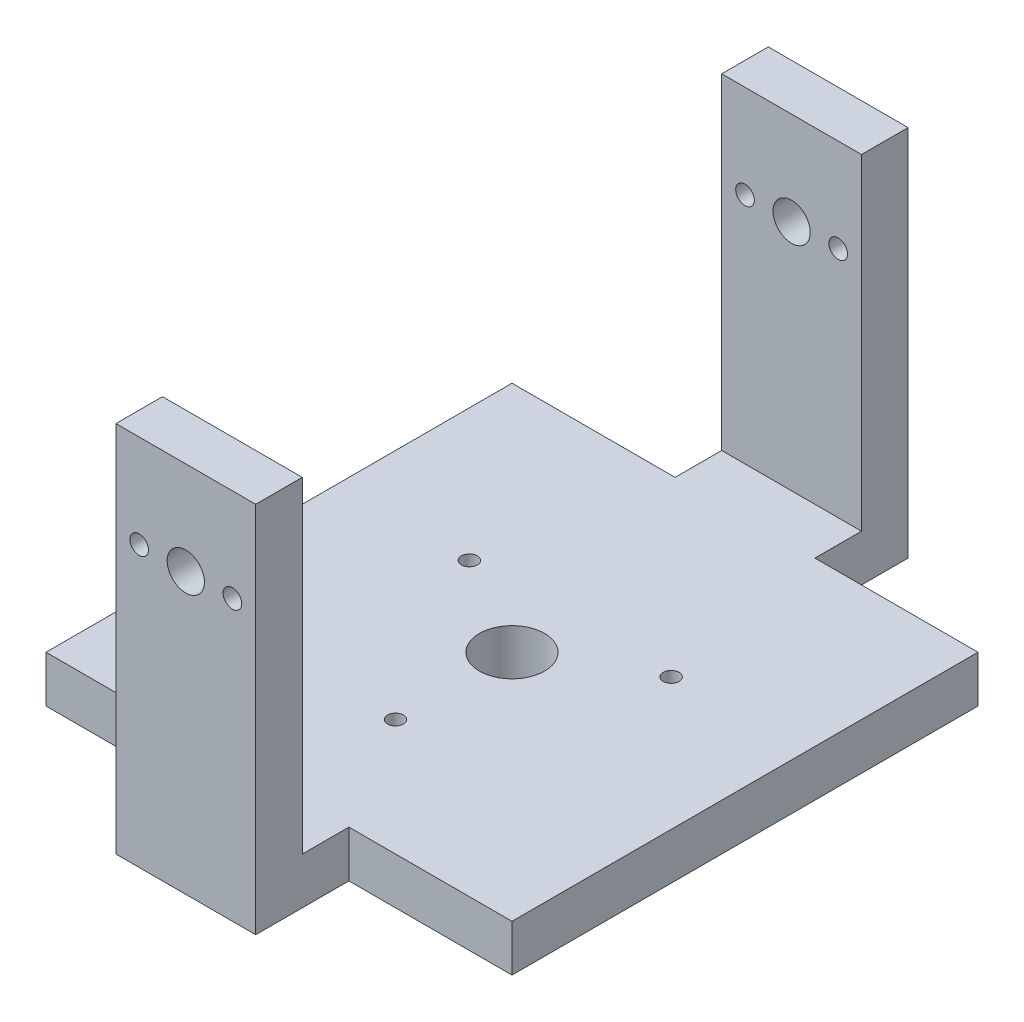
SolidWorks part; units mm, degrees
ref_plane "Plano frontal" through (0, 0, 0) normal (0, 0, 1) x (1, 0, 0)
ref_plane "Plano superior" through (0, 0, 0) normal (0, 1, 0) x (1, 0, 0)
ref_plane "Plano direito" through (0, 0, 0) normal (1, 0, 0) x (0, 0, -1)
sketch "Esboço1" plane through (0, 0, 0) normal (0, 0, 1) x (1, 0, 0)
  line L17 (-15, -50) -> (15, -50)
  line L18 (-15, -50) -> (-15, 20)
  line L19 (-15, 20) -> (15, 20)
  line L20 (15, -50) -> (15, 20)
  line L27 (-15, -50) -> (15, -50)
  line L28 (-15, -50) -> (-15, -60)
  line L29 (-15, -60) -> (15, -60)
  line L30 (15, -50) -> (15, -60)
  line L32 (-50, -50) -> (50, -50)
  line L33 (-50, -50) -> (-50, -60)
  line L34 (-50, -60) -> (50, -60)
  line L35 (50, -50) -> (50, -60)
  circle A0 centre (10, 0) radius 2
  circle A1 centre (-10, 0) radius 2
  circle A2 centre (0, 0) radius 4
extrude "Ressalto-extrusão1" add sketch "Esboço1" along normal blind 10 contours L17 L20 L19 L18 region at (0, -15.5586, 0)
extrude "Ressalto-extrusão3" add sketch "Esboço1<4>" along normal blind 70 contours L30 L17 L28 L29 region at (0, -55, 0)
sketch "Esboço1<4>" plane through (0, 0, 0) normal (0, 0, 1) x (1, 0, 0) same geometry as "Esboço1"
ref_plane "Plano1" through (0, 0, 70) normal (0, 0, 1) x (1, 0, 0)
extrude "Ressalto-extrusão5" add sketch "Esboço1<6>" against normal blind 50 from surface contours L33 L34 L28 L32 | L35 L32 L30 L34 region at (-32.5, -55, 0) region at (32.5, -55, 0) starting at plane "Plano1"
sketch "Esboço1<6>" plane through (0, 0, 0) normal (0, 0, 1) x (1, 0, 0) same geometry as "Esboço1"
mirror "Espelhar2" about plane through (0, 0, 70) normal (0, 0, 1) of "Ressalto-extrusão5", "Ressalto-extrusão3", "Ressalto-extrusão1"
sketch "Esboço3" plane through (0, -50, 0) normal (0, 1, 0) x (1, 0, 0)
  circle A0 centre (0, -70) radius 7
  circle A1 centre (0, -95) radius 3.3
  circle A2 centre (-21.6506, -57.5) radius 3.3
  circle A3 centre (21.6506, -57.5) radius 3.3
  point P11 (0, -70)
  dimension "D1" = 3
extrude "Corte-extrusão1" cut sketch "Esboço3" against normal blind 10 contours A0
sketch "Esboço7" plane through (0, -60, 0) normal (0, -1, 0) x (-1, 0, 0)
  circle A0 centre (0, -95) radius 3.3
  circle A1 centre (-21.6506, -57.5) radius 3.3
  circle A2 centre (21.6506, -57.5) radius 3.3
hole_wizard "Rebaixo para parafuso Allen sextavado de M34" positions "Esboço10" profile "Esboço11" counterbore size "M3" standard "ISO" end condition up to next
sketch "Esboço10" plane through (0, -60, 0) normal (0, -1, 0) x (-1, 0, 0)
  point P0 (-21.6506, -57.5)
  point P3 (21.6506, -57.5)
  point P6 (0, -95)
sketch "Esboço11" plane through (21.6506, -60, 57.5) normal (1, 0, 0) x (0, 0, -1)
  line L0 (0, 0) -> (0, 10)
  line L1 (0, 10) -> (1.7, 10)
  line L3 (1.7, 10) -> (1.7, 3.4)
  line L4 (3.25, 3.4) -> (1.7, 3.4)
  line L5 (3.25, 3.4) -> (3.25, 0.025)
  line L6 (3.25, 0.025) -> (3.275, 0)
  line L7 (3.275, 0) -> (0, 0)
  line L8 (-3.25, 0.025) -> (-3.275, 0) construction
  line L11 (0, -6.35) -> (0, 107.95) construction
  dimension "Thru Hole Dia." = 3.4
  dimension "Thru Hole Depth" = 10
  dimension "C'Bore Dia." = 6.5
  dimension "C'Bore Depth" = 3.4
  dimension "Near C'Sink Dia." = 6.55
  dimension "Near C'Sink Angle" = 90
